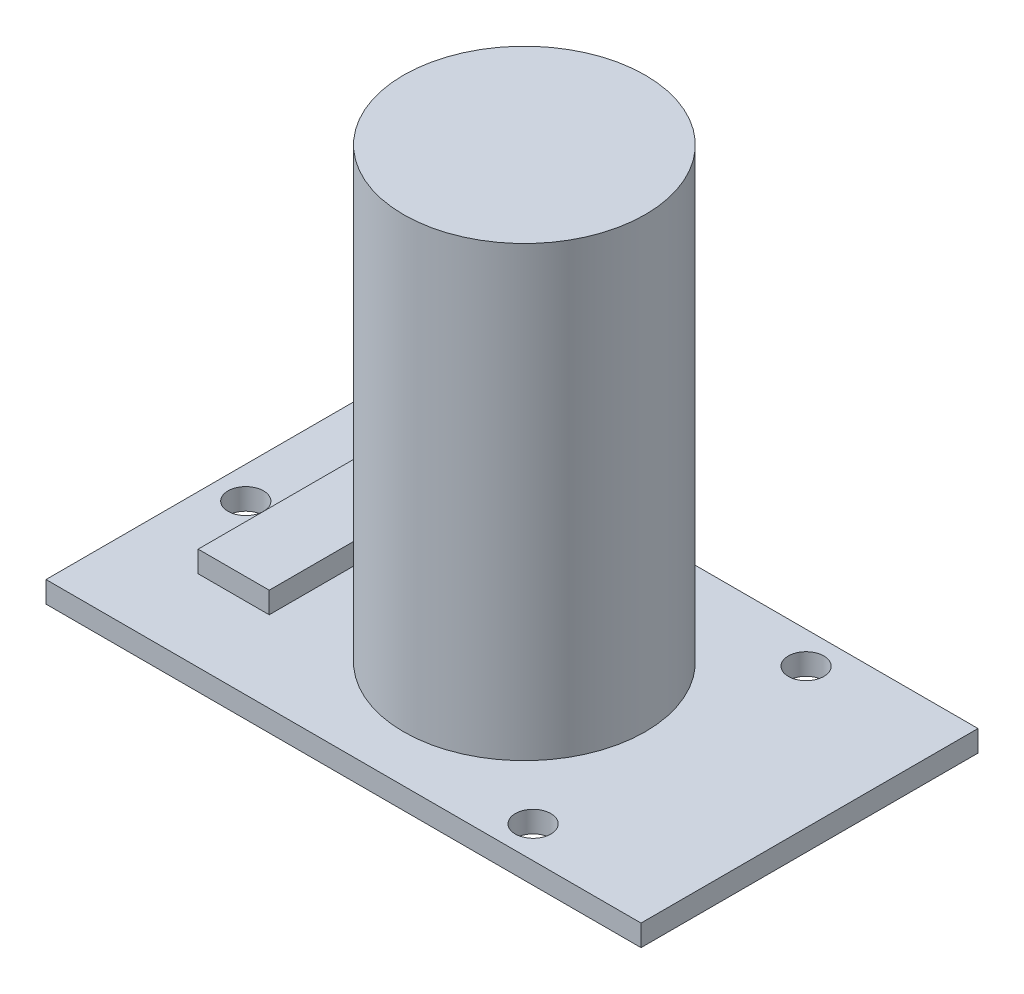
SolidWorks part; units mm, degrees
ref_plane "Front Plane" through (0, 0, 0) normal (0, 0, 1) x (1, 0, 0)
ref_plane "Top Plane" through (0, 0, 0) normal (0, 1, 0) x (1, 0, 0)
ref_plane "Right Plane" through (0, 0, 0) normal (1, 0, 0) x (0, 0, -1)
sketch "Sketch2" plane through (0, 0, 0) normal (0, 1, 0) x (1, 0, 0)
  line L1 (0, 0) -> (41.85, 0)
  line L2 (0, 0) -> (0, -23.7)
  line L3 (0, -23.7) -> (41.85, -23.7)
  line L4 (41.85, 0) -> (41.85, -23.7)
  line L5 (10, -6) -> (5, -6)
  line L6 (10, -6) -> (10, -18)
  line L7 (10, -18) -> (5, -18)
  line L8 (5, -6) -> (5, -18)
  circle A6 centre (32.01, -2.25) radius 1.25
  circle A7 centre (21.85, -11.9023) radius 8.5
  circle A8 centre (32.01, -21.45) radius 1.25
  circle A9 centre (2.2495, -11.898) radius 1.25
  point P27 (0, -11.85)
  dimension "D3" = 2.5
  dimension "D6" = 9.84
  dimension "D12" = 6
  dimension "D4" = 20
  dimension "D5" = 17
  dimension "D7" = 2.25
  dimension "D9" = 2.25
  dimension "D1" = 41.85
  dimension "D2" = 23.7
  dimension "D8" = 2.25
  dimension "D10" = 12
  dimension "D11" = 5
  dimension "5" = 5
extrude "Boss-Extrude1" add sketch "Sketch2" along normal blind 1.5 contours L4 L1 L2 L3 | A6 | L6 L5 L8 L7 region at (20.925, 0, 0.4809)
extrude "Boss-Extrude2" add sketch "Sketch2<3>" along normal blind 33 contours A7 region at (21.85, 0, 11.9023)
sketch "Sketch2<3>" plane through (0, 0, 0) normal (0, 1, 0) x (1, 0, 0) same geometry as "Sketch2"
extrude "Boss-Extrude3" add sketch "Sketch2<6>" along normal blind 3 contours L5 L8 L7 L6 region at (7.5, 0, 12)
sketch "Sketch2<6>" plane through (0, 0, 0) normal (0, 1, 0) x (1, 0, 0) same geometry as "Sketch2"
